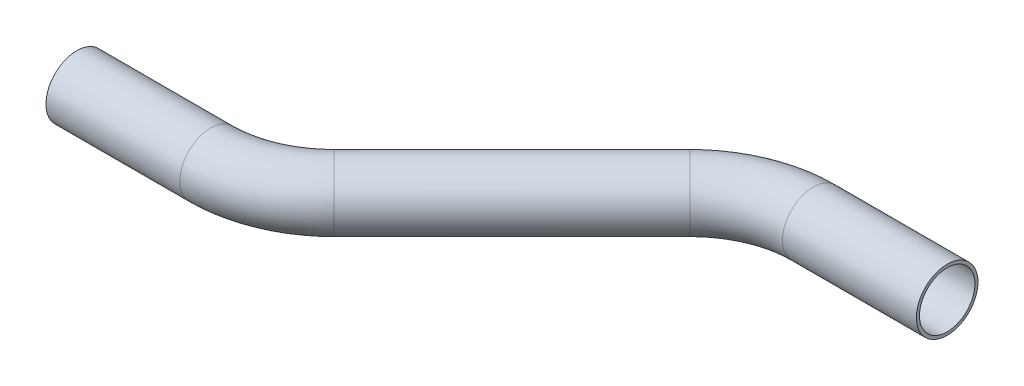
SolidWorks part; units mm, degrees
ref_plane "Front Plane" through (0, 0, 0) normal (0, 0, 1) x (1, 0, 0)
ref_plane "Top Plane" through (0, 0, 0) normal (0, 1, 0) x (1, 0, 0)
ref_plane "Right Plane" through (0, 0, 0) normal (1, 0, 0) x (0, 0, -1)
sketch "Sketch2" plane through (0, 0, 0) normal (0, 1, 0) x (1, 0, 0)
  line L0 (0, 0) -> (27.579, 0)
  line L1 (45.5395, 7.4395) -> (82.2294, 44.1294)
  line L2 (100.1899, 51.5689) -> (127.7689, 51.5689)
  arc A0 (82.2294, 44.1294) -> (100.1899, 51.5689) centre (100.1899, 26.1689) cw
  arc A1 (27.579, 0) -> (45.5395, 7.4395) centre (27.579, 25.4) ccw
  point P7 (89.6689, 51.5689)
  point P10 (38.1, 0)
  dimension "D5" = 25.4
  dimension "D1" = 38.1
  dimension "D2" = 38.1
  dimension "D3" = 51.5689
  dimension "D4" = 135
ref_plane "Plane1" through (0, 0, 0) normal (1, 0, 0) x (0, 0, -1)
sketch "Sketch3" plane through (0, 0, 0) normal (1, 0, 0) x (0, 0, -1)
  circle A0 centre (0, 0) radius 6.35
  circle A1 centre (0, 0) radius 5.715
  dimension "D1" = 12.7
  dimension "D2" = 0.635
sweep "Sweep1" add profiles "Sketch3" path "Sketch2"
